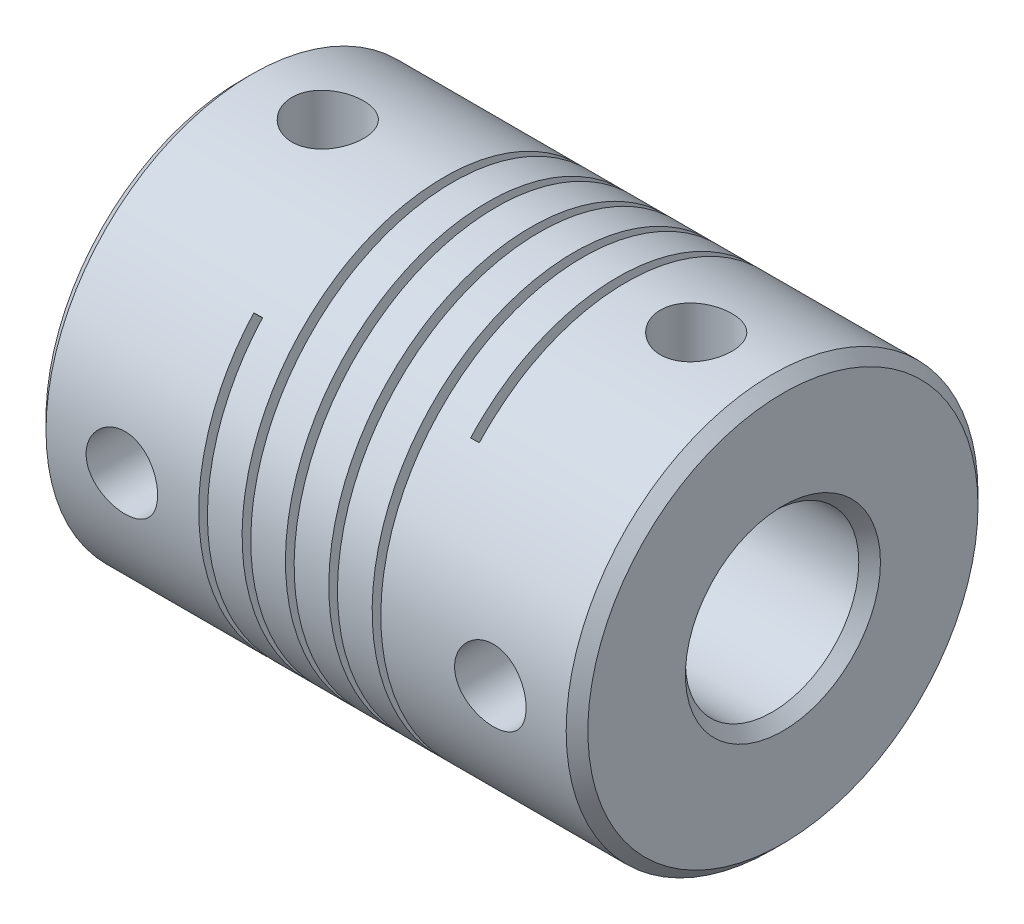
SolidWorks part; units mm, degrees
material "1060 Alloy"
ref_plane "Front Plane" through (0, 0, 0) normal (0, 0, 1) x (1, 0, 0)
ref_plane "Top Plane" through (0, 0, 0) normal (0, 1, 0) x (1, 0, 0)
ref_plane "Right Plane" through (0, 0, 0) normal (1, 0, 0) x (0, 0, -1)
sketch "Sketch1" plane through (0, 0, 0) normal (1, 0, 0) x (0, 0, -1)
  circle A0 centre (0, 0) radius 9.5
  dimension "D1" = 19
extrude "Boss-Extrude1" add sketch "Sketch1" along normal blind 25
sketch "Sketch2" plane through (0, 0, 0) normal (-1, 0, 0) x (0, 0, 1)
  circle A0 centre (0, 0) radius 2.5
  dimension "D1" = 5
extrude "Cut-Extrude1" cut sketch "Sketch2" against normal through all
sketch3d "3DSketch1" plane through (0, 0, 0) normal (0, 0, 1) x (1, 0, 0)
  dimension "D1" = 7.3
sketch "Sketch4" plane through (7.3, 0, 0) normal (-1, 0, 0) x (0, 0, 1)
  circle A0 centre (0, 0) radius 9.5 construction
  circle A1 centre (0, 0) radius 9.5
curve "Helix/Spiral1" pitch 2 height 10 radius 9.5 centre (7.3, 0, 0) axis (1, 0, 0) start towards (0, 0.7071, 0.7071)
ref_plane "Plane1" through (7.3, 6.7175, 6.7175) normal (0.0335, -0.7067, 0.7067) x (0.9994, 0.0237, -0.0237)
sketch "Sketch6" plane through (7.3, 6.7175, 6.7175) normal (0.0335, -0.7067, 0.7067) x (0.9994, 0.0237, -0.0237)
  line L0 (17.6901, 0) -> (-7.2959, 0) construction
  line L1 (0.0041, 0) -> (0.4041, 0)
  line L2 (0.0041, 0) -> (0.0041, -8)
  line L3 (0.0041, -8) -> (0.4041, -8)
  line L4 (0.4041, 0) -> (0.4041, -8)
  ellipse E0 centre (-7.2959, -9.5) end of major axis (-7.2959, -19) minor radius 0.3181 construction
  dimension "D1" = 7.3
  dimension "D2" = 8
  dimension "D3" = 0.4
sweep "Cut-Sweep1" cut profiles "Sketch6" path "Helix/Spiral1" align with end faces yes
sketch "Sketch7" plane through (25, 0, 0) normal (1, 0, 0) x (0, 0, -1)
  circle A0 centre (0, 0) radius 4
  dimension "D1" = 8
extrude "Cut-Extrude2" cut sketch "Sketch7" against normal blind 12.5 contours A0
sketch3d "3DSketch2" plane through (0, 0, 0) normal (0, 0, 1) x (1, 0, 0)
  dimension "D1" = 9.5
sketch "Sketch8" plane through (0, 9.5, 0) normal (0, 1, 0) x (1, 0, 0)
  line L0 (0, 9.5) -> (0, -9.5) construction
  line L1 (8.5535, 9.5) -> (0, 9.5) construction
  circle A0 centre (4, 0) radius 1.65
  dimension "D2" = 3.3
  dimension "D1" = 4
  dimension "D3" = 9.5
extrude "Cut-Extrude3" cut sketch "Sketch8" against normal blind 9
sketch "Sketch9" plane through (0, 0, 0) normal (0, 0, 1) x (1, 0, 0)
  line L0 (27.8015, 0) -> (-3.3633, 0) construction
pattern_circular "CirPattern1" count 2 every 90 about axis through (27.8015, 0, 0) along (-1, 0, 0) of "Cut-Extrude3" reverse direction yes
pattern_linear "LPattern1" count 2 spacing 17 along (1, 0, 0) of "Cut-Extrude3", "CirPattern1"
chamfer "Chamfer1" distance 0.5 angle 45 4 edges at (0, 0, -9.5) (0, 0, 2.5) (25, 0, -9.5) (25, 0, -4)
